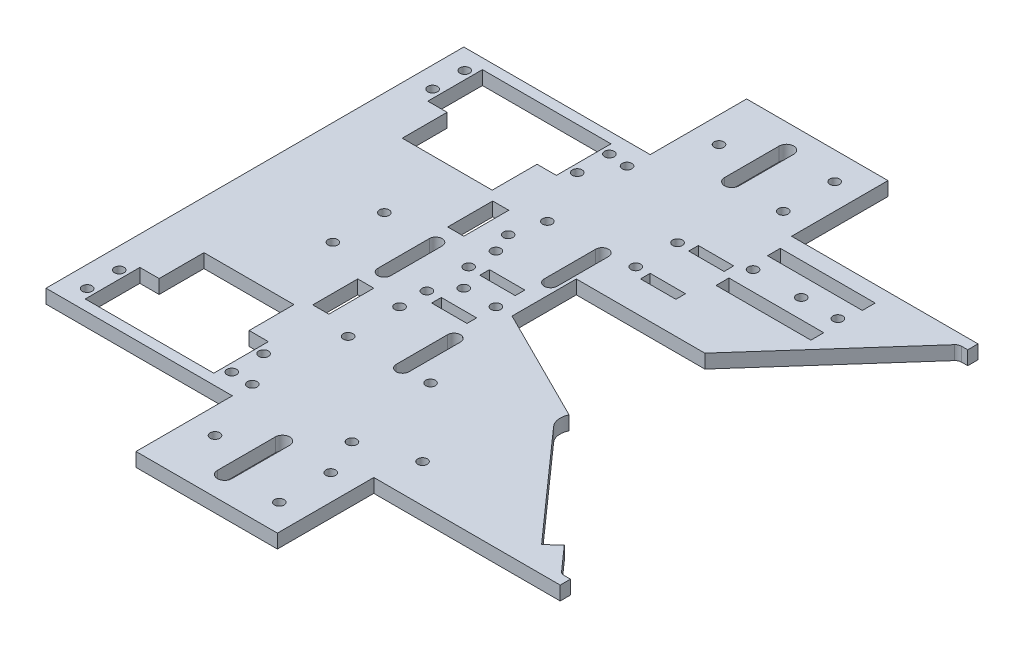
SolidWorks part; units mm, degrees
material "Acrylic (Medium-high impact)"
ref_plane "Front Plane" through (0, 0, 0) normal (0, 0, 1) x (1, 0, 0)
ref_plane "Top Plane" through (0, 0, 0) normal (0, 1, 0) x (1, 0, 0)
ref_plane "Right Plane" through (0, 0, 0) normal (1, 0, 0) x (0, 0, -1)
sketch "Sketch2" plane through (0, 0, 0) normal (0, 1, 0) x (1, 0, 0)
  line L2 (0, 0) -> (0, 65)
  line L3 (0, 65) -> (58, 65)
  line L4 (160, 0) -> (160, 65)
  line L8 (0, 0) -> (160, 0)
  line L9 (102, 65) -> (160, 65)
  line L11 (102, 65) -> (102, 95)
  line L12 (58, 65) -> (58, 95)
  line L13 (58, 95) -> (102, 95)
  dimension "D1" = 65
  dimension "D2" = 160
  dimension "D3" = 44
  dimension "D4" = 30
extrude "Boss-Extrude1" add sketch "Sketch2" along normal blind 4.3
mirror "Mirror1" about plane through (0, 4.3, 0) normal (0, 0, -1) of bodies 101
sketch "Sketch3" plane through (0, 4.3, 0) normal (0, 1, 0) x (1, 0, 0)
  line L0 (160, 61.8) -> (160, -61.8)
  line L1 (120.0126, 20) -> (157.1565, 61.8)
  line L3 (80.0126, 0) -> (80.0126, 20)
  line L4 (80.0126, 20) -> (120.0126, 20)
  line L12 (160, 65) -> (102, 65)
  line L13 (102, 65) -> (102, 95)
  line L15 (102, 95) -> (58, 95)
  line L16 (58, 65) -> (0, 65)
  line L17 (0, 65) -> (0, -65)
  line L18 (0, -65) -> (58, -65)
  line L20 (58, 95) -> (58, 65)
  line L22 (102, -65) -> (160, -65)
  line L23 (160, -65) -> (160, 65)
  line L36 (58, -65) -> (58, -95)
  line L38 (58, -95) -> (102, -95)
  line L39 (58, -95) -> (102, -95)
  line L40 (102, -95) -> (102, -65)
  line L42 (160, -61.8) -> (157.1556, -61.8)
  line L45 (160, 61.8) -> (157.1565, 61.8)
  line L48 (80.0126, 0) -> (120, -20)
  line L49 (120, -20) -> (157.1556, -61.8)
  line M24 (160, -65) -> (160, 65)
  dimension "D2" = 130
  dimension "D3" = 20
  dimension "D4" = 40
  dimension "D1" = 0
extrude "Cut-Extrude1" cut sketch "Sketch3" against normal blind 4.5 contours L48 L49 L1 L4 L3 M24 region at (132.7054, 4.3, -1.1594)
fillet "Fillet1" radius 2 2 edges at (157.1565, 2.15, -61.8) (157.1556, 2.15, 61.8)
ref_axis "Axis1" through (80, 4.3, 95) along (0, 0, -1)
sketch "Sketch4" plane through (0, 4.3, 0) normal (0, 1, 0) x (1, 0, 0)
  line L0 (80, -95) -> (80, 95)
  line L1 (102, -95) -> (58, -95) construction
  line L2 (102, 95) -> (58, 95) construction
ref_plane "Plane2" through (0, 4.3, 0) normal (0, 1, 0) x (1, 0, 0)
sketch "Sketch6" plane through (0, 4.3, 0) normal (0, 1, 0) x (1, 0, 0)
  line L3 (9, -61.8) -> (49, -61.8)
  line L6 (29, -45.8) -> (29, -44.8)
  line L7 (9, -44.8) -> (15, -44.8)
  line L11 (43, -44.8) -> (43, -30.8418)
  line L12 (15, -44.8) -> (15, -30.8418)
  line L13 (15, -30.8418) -> (43, -30.8418)
  line L15 (0, 0) -> (80.0126, 0)
  line L16 (80.0126, 0) -> (120, -20) construction
  line L18 (9, 44.8) -> (15, 44.8)
  line L20 (15, 30.8418) -> (43, 30.8418)
  line L21 (15, 44.8) -> (15, 30.8418)
  line L22 (43, 44.8) -> (43, 30.8418)
  line L25 (15, -45.8) -> (15, -30.8418) construction
  line L27 (9, 61.8) -> (49, 61.8)
  line L30 (4, -61.8) -> (3, -61.8)
  line L31 (0, -61.8) -> (160, -61.8) construction
  line L32 (3, -61.8) -> (4, -61.8)
  line L33 (3, -44.8) -> (3, -62.8) construction
  line L34 (3, -62.8) -> (55, -62.8) construction
  line L35 (55, -44.8) -> (55, -62.8) construction
  line L36 (4, -61.8) -> (54, -61.8) construction
  line L37 (0, 61.8) -> (160, 61.8) construction
  line L38 (54, 61.8) -> (55, 61.8)
  line L39 (54, 61.8) -> (55, 61.8)
  line L40 (43, 44.8) -> (49, 44.8)
  line L41 (4, -45.8) -> (4, -61.8) construction
  line L42 (4, -45.8) -> (54, -45.8) construction
  line L43 (43, -44.8) -> (49, -44.8)
  line L44 (3, -44.8) -> (55, -44.8) construction
  line L45 (29, -45.8) -> (29, -30.8418) construction
  line L46 (43, -45.8) -> (43, -30.8418) construction
  line L47 (54, -45.8) -> (54, -61.8) construction
  line L48 (9, -61.8) -> (49, -61.8)
  line L52 (9, 61.8) -> (9, 44.8)
  line L53 (55, 61.8) -> (54, 61.8)
  line L56 (49, 61.8) -> (49, 44.8)
  line L59 (3, -61.8) -> (4, -61.8)
  line L60 (9, -44.8) -> (9, -61.8)
  line L64 (49, -44.8) -> (49, -61.8)
  dimension "D4" = 1
  dimension "D5" = 14
  dimension "D6" = 14
extrude "Cut-Extrude2" cut sketch "Sketch6" against normal blind 10
sketch "Sketch8" plane through (0, 4.3, 0) normal (0, 1, 0) x (1, 0, 0)
  circle A0 centre (6.5, 58.8) radius 1.5
  circle A1 centre (6.5, 48.8) radius 1.5
  circle A2 centre (51.5, 48.8) radius 1.5
  circle A3 centre (51.5, 58.8) radius 1.5
  circle A4 centre (6.5, -48.7) radius 1.5
  circle A5 centre (6.5, -58.7) radius 1.5
  circle A6 centre (51.5, -58.7) radius 1.5
  circle A7 centre (51.5, -48.8) radius 1.5
  dimension "D7" = 3
extrude "Cut-Extrude3" cut sketch "Sketch8" against normal blind 10
sketch "Sketch9" plane through (0, 0, 0) normal (0, -1, 0) x (1, 0, 0)
  line L0 (75.75, 69.4) -> (75.75, 87.4)
  line L1 (75.75, -87.4) -> (75.75, -70.4)
  line L2 (80.25, -87.4) -> (80.25, -70.4)
  line L4 (80.25, 69.4) -> (80.25, 87.4)
  circle A0 centre (94, 70.4) radius 1.5
  circle A1 centre (66, 78.4) radius 1.5
  circle A2 centre (66, -78.4) radius 1.5
  circle A3 centre (94, -86.4) radius 1.5
  circle A4 centre (94, 86.4) radius 1.5
  circle A5 centre (94, -70.4) radius 1.5
  arc A6 (75.75, -87.4) -> (80.25, -87.4) centre (78, -87.4) ccw
  arc A7 (80.25, -70.4) -> (75.75, -70.4) centre (78, -70.4) ccw
  arc A10 (75.75, 69.4) -> (80.25, 69.4) centre (78, 69.4) ccw
  arc A12 (80.25, 87.4) -> (75.75, 87.4) centre (78, 87.4) ccw
  dimension "D1" = 3
extrude "Cut-Extrude4" cut sketch "Sketch9" against normal blind 10
sketch "Sketch7" plane through (0, 4.3, 0) normal (0, 1, 0) x (1, 0, 0)
  line L0 (0, 0) -> (80.0126, 0)
  line L1 (0, 65) -> (0, -65) construction
  line L2 (80.0126, 0) -> (80.0126, 20) construction
  line L3 (80, -95) -> (80, 95) construction
  line L4 (64, -9) -> (75, -9)
  line L5 (64, -6) -> (75, -6)
  line L6 (64, -9) -> (64, -6)
  line L7 (75, -9) -> (75, -6)
  line L8 (64, -7.5) -> (75, -7.5)
  line L9 (64, 7.5) -> (75, 7.5)
  line L10 (75, 9) -> (75, 6)
  line L11 (64, 9) -> (64, 6)
  line L12 (64, 6) -> (75, 6)
  line L13 (64, 9) -> (75, 9)
  line L14 (89.9874, 30) -> (100.9874, 30)
  line L15 (89.9874, 33) -> (100.9874, 33)
  line L16 (89.9874, 30) -> (89.9874, 33)
  line L17 (100.9874, 30) -> (100.9874, 33)
  line L20 (100.9874, 48) -> (100.9874, 45)
  line L21 (89.9874, 48) -> (89.9874, 45)
  line L22 (89.9874, 45) -> (100.9874, 45)
  line L23 (89.9874, 48) -> (100.9874, 48)
  line L24 (80.0126, 20) -> (120.0126, 20) construction
  circle A0 centre (60.0126, -6.5) radius 1.5
  circle A1 centre (60.0126, 6.5) radius 1.5
  circle A2 centre (86, 32.5) radius 1.5
  circle A3 centre (86, 45.5) radius 1.5
  dimension "D1" = 3
  dimension "D8" = 3
  dimension "D2" = 6.5
  dimension "D3" = 20
  dimension "D6" = 11
  dimension "D4" = 5
  dimension "D5" = 3
  dimension "D7" = 7.5
  dimension "D9" = 11
  dimension "D10" = 3
  dimension "D11" = 12
  dimension "D12" = 13
  dimension "D13" = 10
  dimension "D14" = 3.9874
  dimension "D15" = 0.5
  dimension "D16" = 0.5
  dimension "D17" = 3.9874
  dimension "D18" = 6
  dimension "D19" = 11
sketch "Sketch10" plane through (0, 4.3, 0) normal (0, 1, 0) x (1, 0, 0)
  line L0 (120, -20) -> (156.5589, -61.1287) construction
  line L1 (123.3218, -23.737) -> (149.8964, -53.6334)
  line L2 (116.263, -23.3218) -> (146.1593, -56.9552)
  line L3 (149.8964, -53.6334) -> (146.1593, -56.9552)
  line L4 (120, -20) -> (156.5589, -61.1287) construction
  line L5 (116.263, -23.3218) -> (152.8218, -64.4505) construction
  arc A0 (123.3218, -23.737) -> (116.263, -23.3218) centre (120, -20) ccw
  dimension "D1" = 5
  dimension "D2" = 45
extrude "Cut-Extrude5" cut sketch "Sketch10" against normal blind 10
sketch "Sketch11" plane through (0, 0, 0) normal (0, -1, 0) x (1, 0, 0)
  line L0 (0, 0) -> (80.0126, 0) construction
  line L1 (80, 95) -> (80, -95) construction
  line L2 (80.0126, 0) -> (0, 0)
  line L4 (75, 31.0313) -> (75, 15.0313)
  line L6 (79, 31.0313) -> (79, 15.0313)
  line L7 (79, -31.0313) -> (79, -15.0313)
  line L8 (75, -31.0313) -> (75, -15.0313)
  circle A0 centre (60, 31) radius 1.5
  circle A1 centre (60, 15) radius 1.5
  arc A2 (75, 31.0313) -> (79, 31.0313) centre (77, 31.0313) cw
  arc A3 (75, 15.0313) -> (79, 15.0313) centre (77, 15.0313) ccw
  arc A4 (75, -15.0313) -> (79, -15.0313) centre (77, -15.0313) cw
  arc A5 (75, -31.0313) -> (79, -31.0313) centre (77, -31.0313) ccw
  circle A6 centre (60, -15) radius 1.5
  circle A7 centre (60, -31) radius 1.5
  dimension "D1" = 3
  dimension "D2" = 16
  dimension "D3" = 15
  dimension "D4" = 20
  dimension "D5" = 15
  dimension "D6" = 4
extrude "Cut-Extrude6" cut sketch "Sketch11" against normal blind 10 contours L4 A3 L6 A2 | L8 A5 L7 A4 | A7 | A0 | A1 | A6 region at (77, 0, 23.0313) region at (77, 0, -23.0313) region at (60, 0, -31)
sketch "Sketch12" plane through (0, 0, 0) normal (0, -1, 0) x (-1, 0, 0)
  line L0 (0, 0) -> (-80.0126, 0) construction
  line L3 (-50.2627, -8) -> (-50.2627, 8)
  line L4 (-50.2627, 0) -> (-46.2627, 0)
  line L5 (-46.2627, -8) -> (-46.2627, 8)
  line L6 (0, 0) -> (-46.2627, 0)
  line L7 (0, 65) -> (0, -65) construction
  line L8 (-160, -61.8) -> (0, -61.8) construction
  line L9 (-80.0126, 0) -> (-50.2627, 0)
  line L10 (-80.0126, 0) -> (-115.5281, -17.7634) construction
  line L11 (-80.0126, 0) -> (-80.0126, 20) construction
  line L12 (-58, -65) -> (0, -65) construction
  line L13 (-58, 65) -> (0, 65) construction
  circle A0 centre (-32.2627, -8) radius 1.5
  circle A1 centre (-32.2627, 8) radius 1.5
  arc A2 (-46.2627, 8) -> (-50.2627, 8) centre (-48.2627, 8) ccw
  arc A3 (-50.2627, -8) -> (-46.2627, -8) centre (-48.2627, -8) ccw
  circle A5 centre (-32.2627, -8) radius 1.5 construction
  circle A6 centre (-32.2627, 8) radius 1.5 construction
  dimension "D1" = 3
  dimension "D8" = 8
  dimension "D9" = 8
  dimension "D2" = 8
  dimension "D3" = 14
  dimension "D4" = 4
  dimension "D5" = 61.8
  dimension "D6" = 65
  dimension "D7" = 65
extrude "Cut-Extrude7" cut sketch "Sketch12" against normal blind 10 contours A3 L5 L4 L3 | L4 L5 A2 L3 | A0 | A1 region at (48.2627, 0, 4.7958) region at (48.2627, 0, -4.7958) region at (32.2627, 0, 8) region at (32.2627, 0, -8)
extrude "Cut-Extrude8" cut sketch "Sketch7" against normal blind 9 contours A0 | L4 L7 L5 L6 | L12 L10 L13 L11 | A1 | L23 L20 L22 L21 | L15 L17 L14 L16 | A3 | A2
sketch "Sketch13" plane through (0, 4.3, 0) normal (0, 1, 0) x (1, 0, 0)
  line L0 (80.0126, 0) -> (59.0194, 0)
  line L1 (80, -95) -> (80, 95) construction
  circle A0 centre (65, 0) radius 1.5
  circle A1 centre (75, 0) radius 1.5
  dimension "D2" = 3
  dimension "D3" = 5
  dimension "D1" = 10
extrude "Cut-Extrude9" cut sketch "Sketch13" against normal blind 10 contours L0 A0 | L0 A0 | L0 A1 | L0 A1 region at (75, 4.3, 0.6366) region at (75, 4.3, -0.6366) region at (65, 4.3, 0.6366) region at (65, 4.3, -0.6366)
sketch "Sketch14" plane through (0, 4.3, 0) normal (0, 1, 0) x (1, 0, 0)
  line L0 (160, -65) -> (102, -65) construction
  line L1 (160, -65) -> (160, -61.8) construction
  circle A0 centre (57.5, 58.3) radius 1.5
  circle A2 centre (57.5, 21.3) radius 1.5
  circle A3 centre (85.37, -30.7129) radius 1.5
  circle A4 centre (105.301, -53.1351) radius 1.5
  point P3 (0, 0)
  dimension "D1" = 3
  dimension "D2" = 3
  dimension "D3" = 34.2871
  dimension "D4" = 74.63
  dimension "D5" = 11.8649
  dimension "D6" = 54.699
extrude "Cut-Extrude10" cut sketch "Sketch14" against normal blind 10
sketch "Sketch15" plane through (0, 4.3, 0) normal (0, 1, 0) x (1, 0, 0)
  line L1 (46, 28) -> (51, 28)
  line L2 (46, 28) -> (46, 14)
  line L3 (46, 14) -> (51, 14)
  line L4 (51, 28) -> (51, 14)
  line L6 (0, 65) -> (0, -65) construction
  line L7 (80.0126, 0) -> (53.7017, 0)
  line L8 (46, -14) -> (51, -14)
  line L9 (51, -28) -> (51, -14)
  line L10 (46, -28) -> (51, -28)
  line L11 (46, -28) -> (46, -14)
  arc A0 (50.2627, 8) -> (46.2627, 8) centre (48.2627, 8) ccw construction
  arc A1 (46.2627, -8) -> (50.2627, -8) centre (48.2627, -8) ccw construction
  dimension "D1" = 46
  dimension "D2" = 5
  dimension "D3" = 14
  dimension "D4" = 14
  dimension "D5" = 14
  dimension "D6" = 6
  dimension "D7" = 6
extrude "Cut-Extrude11" cut sketch "Sketch15" against normal blind 10 contours L4 L1 L2 L3 | L11 L10 L9 L8 region at (48.5, 4.3, -21) region at (48.5, 4.3, 21)
sketch "Sketch16" plane through (0, 4.3, 0) normal (0, 1, 0) x (1, 0, 0)
  circle A0 centre (89, -58.8) radius 1.5
  circle A1 centre (58, -58.8) radius 1.5
  dimension "D1" = 3
extrude "Cut-Extrude12" cut sketch "Sketch16" against normal blind 10
ref_plane "Plane3" through (44.2426, 0, 0) normal (1, 0, 0) x (0, 0, -1)
sketch "Sketch17" plane through (44.2426, 0, 0) normal (1, 0, 0) x (0, 0, -1)
  line L4 (0, 0) -> (20, 0)
  line L5 (20, 0) -> (20, 4.3)
  line L6 (20, 4.3) -> (0, 4.3)
  line L7 (0, 4.3) -> (0, 0)
  line L8 (0, 0) -> (20, 0)
  line L9 (20, 0) -> (20, 4.3)
  line L10 (20, 4.3) -> (0, 4.3)
  line L11 (0, 4.3) -> (0, 0)
  circle A0 centre (-2.83, 16.28) radius 0.5
  point P6 (0, 2.15)
  dimension "D4" = 1
  dimension "D2" = 2.83
  dimension "D3" = 14.13
  dimension "D1" = 0
sketch "Sketch18" plane through (0, 4.3, 0) normal (0, 1, 0) x (1, 0, 0)
  line L0 (121.5, 50) -> (129.9, 50)
  line L1 (103.5, 60) -> (133, 60)
  line L2 (102, 65) -> (102, 95) construction
  line L3 (160, 65) -> (102, 65) construction
  line L4 (103.5, 60) -> (103.5, 56)
  line L5 (106.5, 50) -> (118.5, 50)
  line L6 (133, 60) -> (133, 56)
  line L7 (103.5, 60) -> (133, 60)
  line L8 (103.5, 60) -> (103.5, 56)
  line L9 (103.5, 56) -> (133, 56)
  line L10 (133, 60) -> (133, 56)
  line L11 (103.5, 44) -> (133, 44)
  line L12 (133, 40) -> (133, 44)
  line L13 (103.5, 40) -> (133, 40)
  line L14 (103.5, 40) -> (103.5, 44)
  circle A0 centre (105, 50) radius 1.5
  circle A1 centre (120, 50) radius 1.5
  circle A3 centre (131.4, 50) radius 1.5
  dimension "D1" = 3
  dimension "D6" = 3
  dimension "D2" = 15
  dimension "D3" = 29.5
  dimension "D4" = 3
  dimension "D5" = 15
  dimension "D7" = 26.4
  dimension "D8" = 4
  dimension "D9" = 6
extrude "Cut-Extrude13" cut sketch "Sketch18" against normal blind 10 contours L4 L9 L6 L1 | A0 | A1 | A3 | L14 L13 L12 L11 region at (131.4, 4.3, -50) region at (120, 4.3, -50) region at (105, 4.3, -50) region at (118.25, 4.3, -58) region at (118.25, 4.3, -42)
